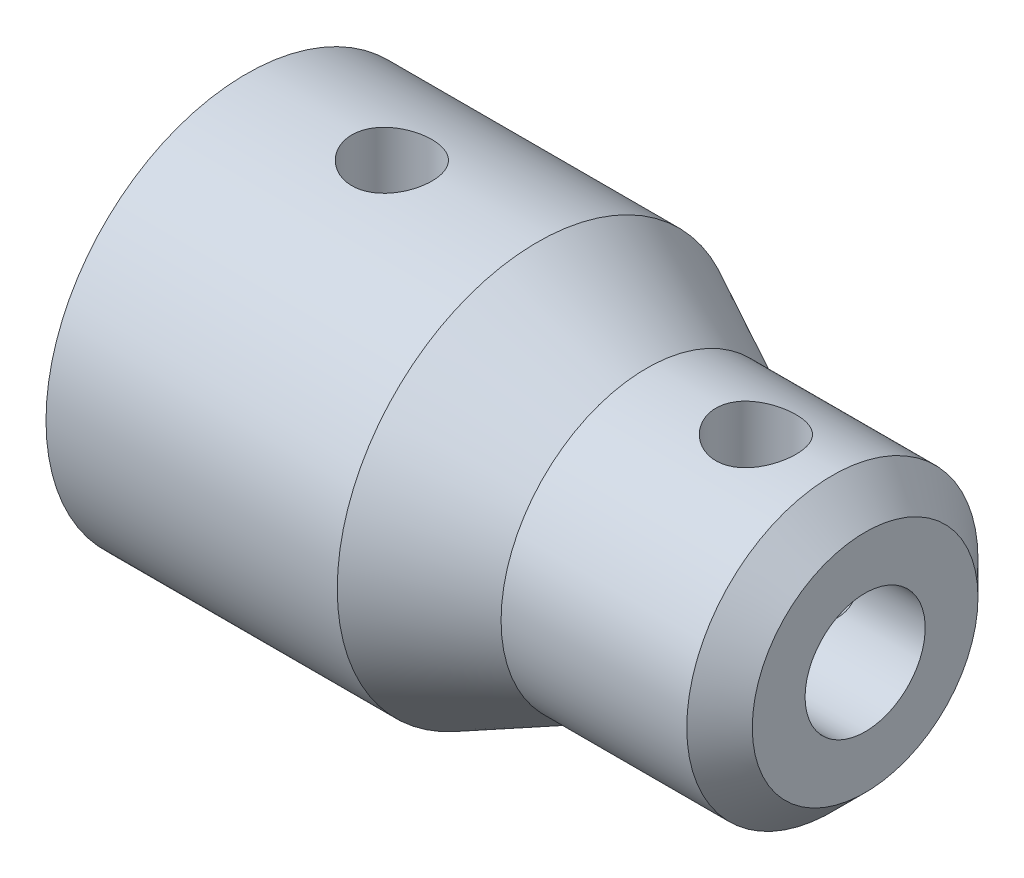
SolidWorks part; units mm, degrees
material "PLA"
ref_plane "Front Plane" through (0, 0, 0) normal (0, 0, 1) x (1, 0, 0)
ref_plane "Top Plane" through (0, 0, 0) normal (0, 1, 0) x (1, 0, 0)
ref_plane "Right Plane" through (0, 0, 0) normal (1, 0, 0) x (0, 0, -1)
sketch "Sketch1" plane through (0, 0, 0) normal (0, 1, 0) x (1, 0, 0)
  line L0 (0, 0) -> (50114.9151, 0) construction
  line L1 (0, -1002.2983) -> (0, 0) construction
  line L2 (-10.16, 3.4036) -> (0, 3.4036)
  line L3 (0, 6.985) -> (3.81, 5.08)
  line L4 (-10.16, 3.4036) -> (-10.16, 6.985)
  line L5 (-10.16, 6.985) -> (0, 6.985)
  line L8 (11.43, 5.08) -> (11.43, 2.0955)
  line L9 (0, 3.4036) -> (0, 50114.9151) construction
  line L10 (0, 3.4036) -> (1.905, 2.0955)
  line L11 (1.905, 2.0955) -> (11.43, 2.0955)
  line L12 (3.81, 5.08) -> (11.43, 5.08)
  line L13 (0.4092, 3.4036) -> (50000.4092, 3.4036) construction
  line L14 (0, 6.985) -> (50000, 6.985) construction
  dimension "D1" = 4.191
  dimension "D2" = 6.8072
  dimension "D3" = 1.905
  dimension "D4" = 13.97
  dimension "D5" = 10.16
  dimension "D6" = 21.59
  dimension "D7" = 10.16
  dimension "D8" = 3.81
revolve "Revolve1" add sketch "Sketch1" angle 360 about L0
sketch "Sketch2" plane through (0, 0, 0) normal (0, 1, 0) x (1, 0, 0)
  line L0 (0, 0) -> (50000, 0) construction
  line L1 (0, 6.985) -> (-10.16, 6.985) construction
  line L2 (-5.08, 6.985) -> (-5.08, 0) construction
  line L3 (7.62, 5.08) -> (7.62, 0) construction
  line L4 (11.43, 5.08) -> (3.81, 5.08) construction
  circle A0 centre (-5.08, 0) radius 1.397
  circle A1 centre (7.62, 0) radius 1.397
  dimension "D1" = 2.794
  dimension "D2" = 2.794
extrude "Cut-Extrude1" cut sketch "Sketch2" along normal through all
pattern_circular "CirPattern1" count 2 every 90 about axis through (-10.16, 0, 0) along (-1, 0, 0) of "Cut-Extrude1"
chamfer "Chamfer1" distance 1.143 angle 45 1 edges at (11.43, 0, 5.08)
equation "\"D2@Sketch2\"=\"D1@Sketch2\""
